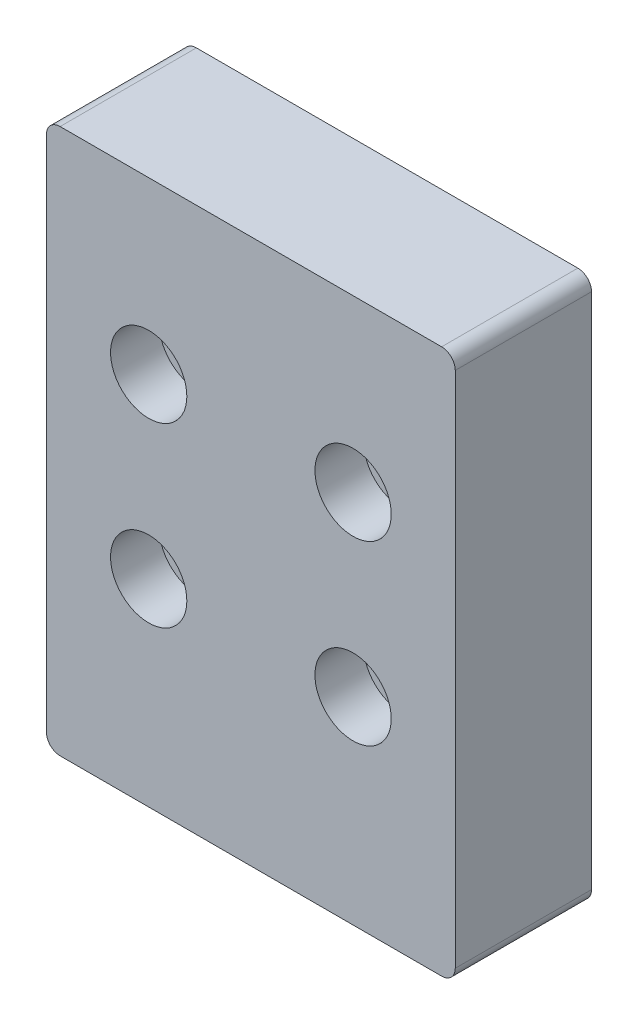
SolidWorks part; units mm, degrees
material "ABS"
ref_plane "Front Plane" through (0, 0, 0) normal (0, 0, 1) x (1, 0, 0)
ref_plane "Top Plane" through (0, 0, 0) normal (0, 1, 0) x (1, 0, 0)
ref_plane "Right Plane" through (0, 0, 0) normal (1, 0, 0) x (0, 0, -1)
sketch "Sketch1" plane through (0, 0, 0) normal (0, 0, 1) x (1, 0, 0)
  line L1 (-15, -20) -> (15, -20)
  line L2 (-15, -20) -> (-15, 20)
  line L3 (-15, 20) -> (15, 20)
  line L4 (15, -20) -> (15, 20)
  line L5 (-15, -20) -> (15, 20) construction
  line L6 (-15, 20) -> (15, -20) construction
  point P0 (0, 0)
  dimension "D1" = 40
  dimension "D2" = 30
extrude "Body" add sketch "Sketch1" along normal mid plane 10
hole_wizard "CBORE for M2 Hex Head Bolt2" positions "Sketch5" profile "Sketch6" counterbore size "M5" standard "ANSI Metric"
sketch "Sketch5" plane through (0, 0, 5) normal (0, 0, 1) x (1, 0, 0)
  line L1 (-7.5, 7.5) -> (7.5, 7.5) construction
  line L3 (15, 20) -> (-15, 20) construction
  point P0 (-7.5, 7.5)
  point P3 (7.5, 7.5)
  point P10 (0, 7.5)
  dimension "D1" = 15
  dimension "D2" = 12.5
sketch "Sketch6" plane through (-7.5, 7.5, 5) normal (1, 0, 0) x (0, -1, 0)
  line L0 (0, 0) -> (0, 10.7811)
  line L1 (0, 10.7811) -> (1.3, 10)
  line L2 (1.3, 10) -> (1.3, 3.58)
  line L3 (1.3, 3.58) -> (2.8, 3.58)
  line L4 (2.8, 3.58) -> (2.8, 0)
  line L5 (2.8, 0) -> (0, 0)
  line L10 (0, 10.7811) -> (-1.3, 10) construction
  line L11 (0, -6.35) -> (0, 107.95) construction
  dimension "Hole Dia." = 2.6
  dimension "Hole Depth" = 10
  dimension "C'Bore Dia." = 5.6
  dimension "C'Bore Depth" = 3.58
  dimension "Drill Angle" = 118
pattern_linear "LPattern1" count 2 spacing 13 along (0, -1, 0) of "CBORE for M2 Hex Head Bolt2"
fillet "Fillet1" radius 1 4 edges at (15, 20, 0) (15, -20, 0) (-15, -20, 0) (-15, 20, 0)
